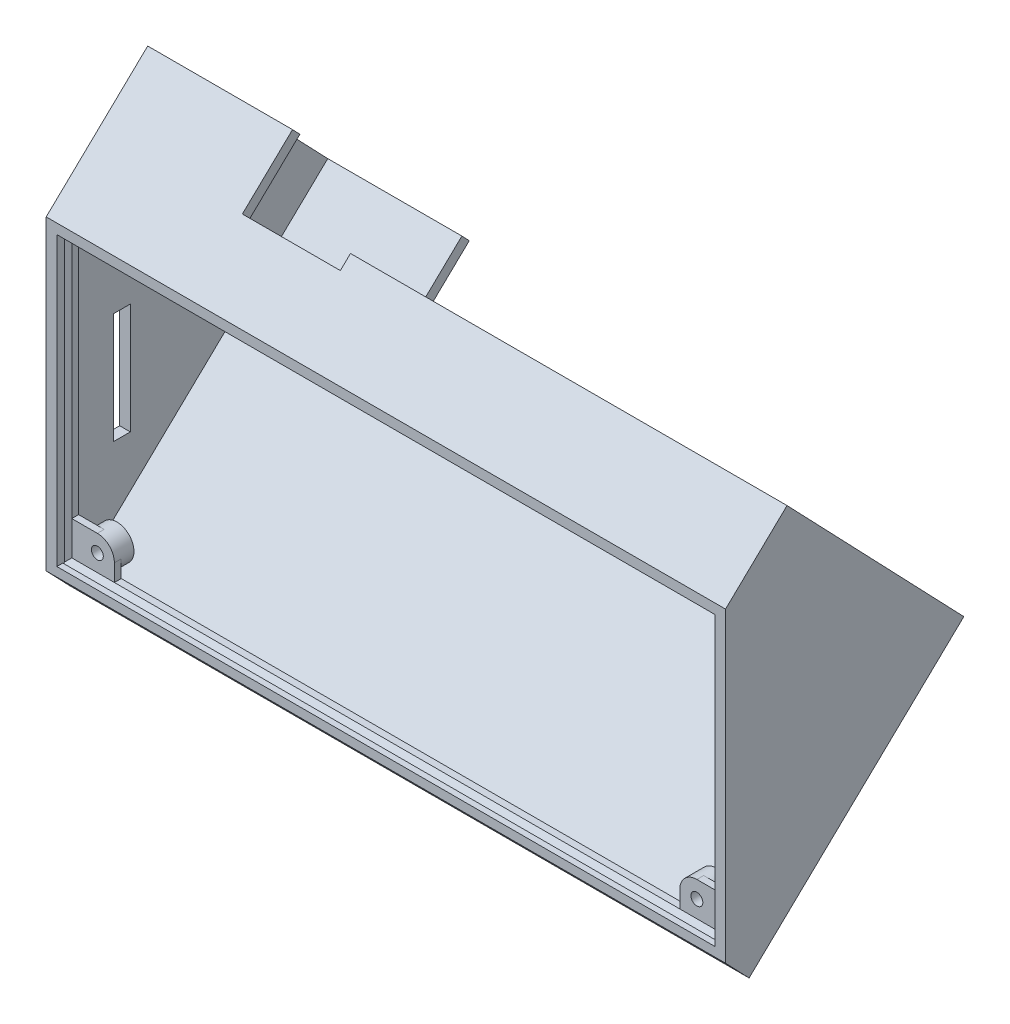
SolidWorks part; units mm, degrees
material "ABS"
ref_plane "Front Plane" through (0, 0, 0) normal (0, 0, 1) x (1, 0, 0)
ref_plane "Top Plane" through (0, 0, 0) normal (0, 1, 0) x (1, 0, 0)
ref_plane "Right Plane" through (0, 0, 0) normal (1, 0, 0) x (0, 0, -1)
sketch "Sketch1" plane through (0, 0, 0) normal (0, 0, 1) x (1, 0, 0)
  line L0 (-81.1699, 37.1521) -> (78.3301, 37.1521)
  line L1 (-78.6699, -32.8479) -> (75.8301, -32.8479)
  line L2 (-78.6699, -32.8479) -> (-78.6699, 34.6521)
  line L3 (-78.6699, 34.6521) -> (75.8301, 34.6521)
  line L4 (75.8301, -32.8479) -> (75.8301, 34.6521)
  line L5 (-78.6699, -32.8479) -> (75.8301, 34.6521) construction
  line L6 (-78.6699, 34.6521) -> (75.8301, -32.8479) construction
  line L7 (78.3301, -35.3479) -> (78.3301, 37.1521)
  line L8 (-81.1699, -35.3479) -> (78.3301, -35.3479)
  line L9 (-81.1699, -35.3479) -> (-81.1699, 37.1521)
  line L10 (-78.4199, 34.4021) -> (75.5801, 34.4021) construction
  line L11 (-78.4199, -32.5979) -> (-78.4199, 34.4021) construction
  line L13 (75.5801, 34.4021) -> (75.5801, -32.5979) construction
  line L14 (75.5801, -32.5979) -> (-78.4199, -32.5979) construction
  point P0 (0, 0)
  dimension "D2" = 0.25
  dimension "D3" = 0.25
  dimension "D4" = 0.25
  dimension "D5" = 0.25
  dimension "D1" = 2.5
ref_plane "Plane1" through (-81.1699, 0, 0) normal (1, 0, 0) x (0, 1, 0)
sketch "Sketch3" plane through (-81.1699, 0, 0) normal (1, 0, 0) x (0, 1, 0)
  line L0 (37, 0) -> (50.8332, -14.4444)
  line L1 (-35.3479, 0) -> (37.1521, 0) construction
  line L2 (-35.3479, 0) -> (37.1521, 0) construction
  line L3 (50.8332, -14.4444) -> (7.4999, -55.9441)
  line L4 (-35, 0) -> (-40.7778, -5.5333)
  line L5 (-40.7778, -5.5333) -> (7.4999, -55.9441)
  line L6 (37, 0) -> (-35, 0)
  dimension "D1" = 72
  dimension "D2" = 20
  dimension "D3" = 8
  dimension "D4" = 60
  dimension "D5" = 35
extrude "Boss-Extrude3" add sketch "Sketch3" along normal up to vertex (159.5 mm away) up to point (78.3301, 37.1521, 0)
shell "Shell1" thickness 2.5 removed face at (-1.4199, 1, 0)
extrude "Cut-Extrude2" cut sketch "Sketch1" against normal blind 4 contours L3 L4 L1 L2
sketch "Sketch2" plane through (-81.1699, 0, 0) normal (-1, 0, 0) x (0, 0, 1)
  line L1 (-17.25, -14.0979) -> (-13.25, -14.0979)
  line L2 (-17.25, -14.0979) -> (-17.25, 11.9021)
  line L3 (-17.25, 11.9021) -> (-13.25, 11.9021)
  line L4 (-13.25, -14.0979) -> (-13.25, 11.9021)
  line L5 (-17.25, -14.0979) -> (-13.25, 11.9021) construction
  line L6 (-17.25, 11.9021) -> (-13.25, -14.0979) construction
  point P0 (-15.25, -1.0979)
  dimension "D1" = 1.0979
  dimension "D2" = 4
  dimension "D3" = 26
  dimension "D4" = 15.25
extrude "Cut-Extrude1" cut sketch "Sketch2" against normal up to next
ref_plane "Plane2" through (0, 0, -1.8) normal (0, 0, 1) x (1, 0, 0)
sketch "Sketch6" plane through (0, 0, -1.8) normal (0, 0, 1) x (1, 0, 0)
  line L0 (-78.6699, 34.6521) -> (75.8301, 34.6521) construction
  line L1 (-78.6699, 34.6521) -> (-78.6699, -32.8479) construction
  line L2 (-78.6699, -32.8479) -> (75.8301, -32.8479) construction
  line L3 (75.8301, 34.6521) -> (75.8301, -32.8479) construction
  line L4 (-78.6699, 34.6521) -> (75.8301, 34.6521)
  line L5 (-78.6699, 34.6521) -> (-78.6699, -32.8479)
  line L6 (-78.6699, -32.8479) -> (75.8301, -32.8479)
  line L7 (75.8301, 34.6521) -> (75.8301, -32.8479)
sketch "Sketch7" plane through (75.8301, 0, 0) normal (-1, 0, 0) x (0, 0, 1)
  line L0 (-1.3568, 35.1148) -> (-2.6364, 33.7787)
  line L1 (-2.6364, 33.7787) -> (-4.2364, 33.7787)
  line L2 (-4.2364, 33.7787) -> (-4.2364, 37.8725)
  line L3 (-4.2364, 37.8725) -> (-1.3568, 35.1148)
  line L4 (-14.368, 47.2985) -> (-1.1628, 34.6521) construction
  dimension "D1" = 90
  dimension "D2" = 0.2
  dimension "D3" = 1.65
  dimension "D4" = 1.6
sweep "Sweep1" add profiles "Sketch7" path "Sketch6"
sketch "Sketch8" plane through (0, 0, 0) normal (0, 0, 1) x (1, 0, 0)
  line L0 (-91.1699, 60.8332) -> (88.3301, 60.8332)
  line L1 (-81.1699, 50.8332) -> (78.3301, 50.8332)
  line L2 (-81.1699, 50.8332) -> (-81.1699, -40.7778)
  line L3 (-81.1699, -40.7778) -> (78.3301, -40.7778)
  line L4 (78.3301, 50.8332) -> (78.3301, -40.7778)
  line L5 (88.3301, 60.8332) -> (88.3301, -50.7778)
  line L6 (-91.1699, -50.7778) -> (88.3301, -50.7778)
  line L7 (-91.1699, 60.8332) -> (-91.1699, -50.7778)
  dimension "D1" = 10
extrude "Cut-Extrude3" cut sketch "Sketch8" against normal through all
sketch "Sketch10" plane through (0, 31.5338, -32.9272) normal (0, 0.6917, -0.7222) x (-1, 0, 0)
  line L0 (78.6699, -30.7778) -> (78.6699, 24.2222)
  line L1 (81.1699, -33.2778) -> (47.1699, -33.2778)
  line L2 (81.1699, -33.2778) -> (81.1699, 26.7222)
  line L3 (81.1699, 26.7222) -> (47.1699, 26.7222)
  line L4 (47.1699, -33.2778) -> (47.1699, -30.7778)
  line L5 (78.6699, 24.2222) -> (47.1699, 24.2222)
  line L6 (78.6699, -30.7778) -> (78.6699, 24.2222) construction
  line L7 (78.6699, -30.7778) -> (47.1699, -30.7778)
  line L8 (49.6699, -30.7778) -> (49.6699, 24.2222) construction
  line L9 (78.6699, 24.2222) -> (49.6699, 24.2222) construction
  line L10 (78.6699, -30.7778) -> (49.6699, -30.7778) construction
  line L11 (47.1699, 24.2222) -> (47.1699, 26.7222)
  line L12 (47.1699, -33.2778) -> (47.1699, 26.7222) construction
  line L13 (47.1699, 24.2222) -> (47.1699, -30.7778)
  line M1 (81.1699, -33.2778) -> (81.1699, 26.7222)
  line M2 (81.1699, 26.7222) -> (-78.3301, 26.7222)
  line M4 (-78.3301, -33.2778) -> (81.1699, -33.2778)
  dimension "D1" = 34
extrude "Cut-Extrude4" cut sketch "Sketch10" against normal up to surface (2.5 mm away) contours L5 L13 L7 L0 region at (-62.9199, 29.1666, -35.1943) up to face at (-1.4199, 27.4374, -33.3887)
extrude "Boss-Extrude4" add sketch "Sketch10<3>" along normal blind 13 contours L11 L5 L0 L7 L4 M4 M1 M2 region at (-79.3596, 29.1666, -35.1943)
sketch "Sketch10<3>" plane through (0, 31.5338, -32.9272) normal (0, 0.6917, -0.7222) x (-1, 0, 0) same geometry as "Sketch10"
sketch "Sketch12" plane through (0, 31.5338, -32.9272) normal (0, 0.6917, -0.7222) x (-1, 0, 0)
  line L0 (47.1699, -33.2778) -> (-15.8301, -33.2778)
  line L1 (-78.3301, -33.2778) -> (47.1699, -33.2778) construction
  line L2 (-15.8301, -33.2778) -> (-15.8301, -13.2778)
  line L3 (-15.8301, -13.2778) -> (24.1699, 26.7222)
  line L4 (-78.3301, 26.7222) -> (47.1699, 26.7222) construction
  line L5 (24.1699, 26.7222) -> (47.1699, 26.7222)
  line L6 (47.1699, 26.7222) -> (47.1699, -33.2778)
  dimension "D1" = 63
  dimension "D2" = 135
  dimension "D3" = 20
extrude "Cut-Extrude5" cut sketch "Sketch12" against normal blind 3.302
sketch "Sketch13" plane through (0, 31.5338, -32.9272) normal (0, 0.6917, -0.7222) x (-1, 0, 0)
  line L0 (-78.3301, -23.2778) -> (-15.8301, -23.2778) construction
  line L1 (-78.3301, -33.2778) -> (-78.3301, 26.7222) construction
  line L2 (-78.3301, -33.2778) -> (-15.8301, -33.2778) construction
  line L4 (-15.8301, -13.2778) -> (-15.8301, -33.2778) construction
  circle A0 centre (-68.3301, -23.2778) radius 2.6
  circle A1 centre (-33.3301, -23.2778) radius 2.6
  circle A2 centre (1.6699, -23.2778) radius 2.6 [skipped]
  circle A3 centre (-33.3301, 16.7222) radius 2.6
  circle A4 centre (1.6699, 16.7222) radius 2.6
  circle A5 centre (-68.3301, 16.7222) radius 2.6
  dimension "D1" = 5.2
  dimension "D2" = 10
  dimension "D6" = 40
  dimension "D7" = 35
  dimension "D3" = 10
  dimension "D4" = 3
  dimension "D5" = 2
extrude "Cut-Extrude6" cut sketch "Sketch13" against normal up to surface (2.5 mm away) up to face at (32.3301, 25.993, -34.772)
sketch "Sketch14" plane through (0, 0, -4.2364) normal (0, 0, -1) x (-1, 0, 0)
  line L0 (1.4199, -31.9746) -> (1.4199, -9.1254) construction
  line L1 (77.7966, -31.9746) -> (67.7966, -31.9746)
  line L2 (77.7966, -31.9746) -> (77.7966, -23.9746)
  line L3 (77.7966, -23.9746) -> (71.7966, -23.9746)
  line L4 (67.7966, -31.9746) -> (67.7966, -27.9746)
  line L5 (77.7966, -31.9746) -> (-74.9567, -31.9746) construction
  line L6 (-74.9567, -31.9746) -> (-64.9567, -31.9746)
  line L7 (-64.9567, -31.9746) -> (-64.9567, -27.9746)
  line L8 (-74.9567, -23.9746) -> (-68.9567, -23.9746)
  line L9 (-74.9567, -31.9746) -> (-74.9567, -23.9746)
  arc A0 (71.7966, -23.9746) -> (67.7966, -27.9746) centre (71.7966, -27.9746) ccw
  arc A1 (-68.9567, -23.9746) -> (-64.9567, -27.9746) centre (-68.9567, -27.9746) cw
  point P7 (67.7966, -23.9746)
  point P12 (1.4199, -31.9746)
  dimension "D3" = 4
  dimension "D1" = 8
  dimension "D2" = 10
extrude "Boss-Extrude5" add sketch "Sketch14" against normal up to vertex (1.6 mm away) up to point (74.9567, -31.9746, -2.6364)
sketch "Sketch15" plane through (0, 0, -4.2364) normal (0, 0, -1) x (-1, 0, 0)
  circle A0 centre (71.7966, -27.9746) radius 4
  circle A1 centre (71.7966, -27.9746) radius 1.4
  arc A2 (71.7966, -23.9746) -> (67.7966, -27.9746) centre (71.7966, -27.9746) ccw construction
  circle A3 centre (-68.9567, -27.9746) radius 4
  circle A4 centre (-68.9567, -27.9746) radius 1.4
  arc A5 (-64.9567, -27.9746) -> (-68.9567, -23.9746) centre (-68.9567, -27.9746) ccw construction
  dimension "D1" = 2.8
extrude "Boss-Extrude6" add sketch "Sketch15" along normal blind 3
extrude "Cut-Extrude7" cut sketch "Sketch15<2>" against normal up to next contours A4 | A1
sketch "Sketch15<2>" plane through (0, 0, -4.2364) normal (0, 0, -1) x (-1, 0, 0) same geometry as "Sketch15"
sketch "Sketch16" plane through (0, 0, 0) normal (0, 0, 1) x (1, 0, 0)
  line L0 (78.3301, 37) -> (-81.1699, 37) construction
  line L1 (78.3301, -35) -> (-81.1699, -35) construction
  line L2 (70.8301, -35) -> (78.3301, -35)
  line L3 (78.3301, 29.5) -> (78.3301, 37)
  line L4 (6.0801, 37) -> (-8.9199, 37)
  line L5 (-73.6699, 37) -> (-81.1699, 37)
  line L6 (-81.1699, 37) -> (-81.1699, -35)
  line L7 (-81.1699, -35) -> (78.3301, -35)
  line L8 (78.3301, -35) -> (78.3301, 37)
  line L9 (78.3301, 37) -> (-81.1699, 37)
  line L10 (-81.1699, 37) -> (-81.1699, 29.5)
  line L11 (-81.1699, -35) -> (-73.6699, -35)
  line L12 (78.3301, -35) -> (78.3301, -27.5)
  line L13 (78.3301, 37) -> (70.8301, 37)
  line L14 (-81.1699, -27.5) -> (-81.1699, -35)
  line L15 (-8.9199, -35) -> (6.0801, -35)
  arc A0 (-73.6699, 37) -> (-81.1699, 29.5) centre (-81.1699, 37) ccw
  arc A1 (78.3301, 29.5) -> (70.8301, 37) centre (78.3301, 37) ccw
  arc A2 (70.8301, -35) -> (78.3301, -27.5) centre (78.3301, -35) ccw
  arc A3 (-81.1699, -27.5) -> (-73.6699, -35) centre (-81.1699, -35) ccw
  arc A4 (6.0801, 37) -> (-8.9199, 37) centre (-1.4199, 37) ccw
  arc A5 (-8.9199, -35) -> (6.0801, -35) centre (-1.4199, -35) ccw
  dimension "D1" = 15
  dimension "D2" = 0
extrude "Pads For Printing" [suppressed] add sketch "Sketch16" against normal blind 0.3
